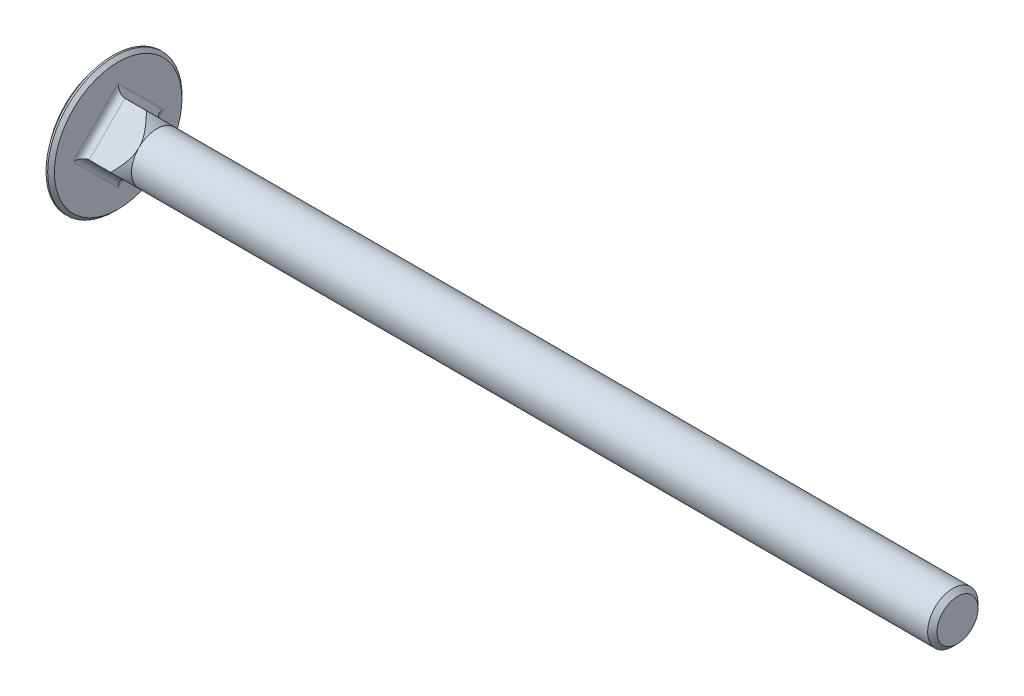
SolidWorks part; units mm, degrees
revolve "Base-Revolve" add sketch "BodySke" angle 360 about L6 other way angle 60
sketch "BodySke" plane through (0, 0, 0) normal (0, 0, 1) x (1, 0, 0)
  line L1 (3.0024, 8) -> (3.6, 8)
  line L2 (3.6, 8) -> (3.6, 3)
  line L3 (3.6, 3) -> (103.0455, 3)
  line L4 (103.6, 2.4455) -> (103.6, 0)
  line L5 (103.6, 0) -> (0, 0)
  line L6 (-31.75, 0) -> (127, 0) construction
  line L8 (103.6, 2.4455) -> (103.0455, 3)
  line L10 (103.6, -2.4455) -> (103.0455, -3) construction
  line L11 (4.6, 7.799) -> (4.6, 1.449) construction
  line L12 (85.6, 7.799) -> (85.6, 1.449) construction
  line L13 (3.6, 7.799) -> (3.6, 1.449) construction
  arc A0 (3.0024, 8) -> (0, 0) centre (12.1593, 0) ccw
  dimension "Diameter" = 6
  dimension "Head_dia" = 16
  dimension "Head_ht" = 3.6
  dimension "D1" = 0.5976
cosmetic thread "ThreadCosmetic" [suppressed] parameters "Thread_length"=18, "Thread_minor"=4.891
ref_plane "Plane1" through (0, 0, 0) normal (0, 0, 1) x (1, 0, 0)
ref_plane "Plane2" through (0, 0, 0) normal (0, 1, 0) x (1, 0, 0)
ref_plane "Plane3" through (0, 0, 0) normal (1, 0, 0) x (0, 0, -1)
sketch "Sketch1" plane through (3.6, 0, 0) normal (1, 0, 0) x (0, 0, -1)
  line L0 (0, 4.2426) -> (4.2426, 0)
  line L1 (4.2426, 0) -> (0, -4.2426)
  line L2 (0, -4.2426) -> (-4.2426, 0)
  line L3 (-4.2426, 0) -> (0, 4.2426)
  circle A0 centre (0, 0) radius 3 construction
  circle A1 centre (0, 0) radius 8 construction
  dimension "D1" = 6
extrude "Boss-Extrude1" add sketch "Sketch1" along normal blind 4.6
sketch "Sketch2" plane through (0, 0, 0) normal (0, 0, 1) x (1, 0, 0)
  line L0 (0, 0) -> (101.6, 0) construction
  line L1 (8.2, 3) -> (13.2, 3)
  line L2 (8.2, 3) -> (2.2, 9)
  line L3 (13.2, 3) -> (13.2, 9)
  line L4 (13.2, 9) -> (2.2, 9)
  dimension "D1" = 6
  dimension "D2" = 8.2
  dimension "D3" = 18
  dimension "D4" = 5
  dimension "D5" = 45
revolve "Cut-Revolve1" cut sketch "Sketch2" angle 360 about L0
fillet "Fillet1" radius 0.8 4 edges at (3.6, 2.1213, 2.1213) (3.6, -2.1213, 2.1213) (3.6, -2.1213, -2.1213) (3.6, 2.1213, -2.1213)
sketch "ThdSchSke" plane through (0, 0, 0) normal (0, 0, 1) x (1, 0, 0)
  line L0 (85.6, -2.4455) -> (85.2117, -3)
  line L1 (85.6, -2.4455) -> (85.9883, -3)
  line L2 (85.9883, -3) -> (85.9883, -3.75)
  line L3 (0, 0) -> (5.1513, 0) construction
  line L5 (85.9883, -3.75) -> (85.2117, -3.75)
  line L6 (85.2117, -3.75) -> (85.2117, -3)
  arc A0 (3.0024, 8) -> (3.0024, -8) centre (12.1593, 0) ccw construction
  dimension "Diameter" = 6
  dimension "Thread_minor" = 4.891
  dimension "Start" = 85.6
revolve "ThreadSchematic" [suppressed] cut sketch "ThdSchSke" angle 360 about L3
pattern_linear "ThdSchPat" [suppressed]
equation "\"Thread_minor@ThreadCosmetic\"  =  \"Minor_dia@BodySke\""
equation "\"Thread_length@ThreadCosmetic\" = ((sgn( (\"Length@BodySke\" - \"Advance@BodySke\" * 3.0) - \"Thread_nom@BodySke\" )-1)*( (\"Length@BodySke\" - \"Advance@BodySke\" * 3.0) - \"Thread_nom@BodySke\" ))/-2+ \"Thread_nom@BodySke\""
equation "\"Thread_minor@ThdSchSke\" = \"Minor_dia@BodySke\""
equation "\"Diameter@ThdSchSke\" = \"Diameter@BodySke\""
equation "\"Overcut@ThdSchSke\" = \"Diameter@BodySke\" * 1.25"
equation "\"Start@ThdSchSke\" = \"Head_ht@BodySke\" + \"Length@BodySke\" - \"Thread_length@ThreadCosmetic\"  '---Non-countersunk---"
equation "\"Num_threads@ThdSchPat\" = int( \"Thread_length@ThreadCosmetic\" / \"Advance@BodySke\" + 0.999 )  + 1"
equation "\"Advance@ThdSchPat\" = \"Thread_length@ThreadCosmetic\" /  (\"Num_threads@ThdSchPat\" - 1) 'relax it"
equation "\"Num_threads@ThdSchPat\" = \"Num_threads@ThdSchPat\" - sgn( \"Num_threads@ThdSchPat\" - 1) '---chamfered tips only---"
equation "\"D1@BodySke\" = \"Head_ht@BodySke\" * .166"
equation "\"D1@Sketch2\" = \"Diameter@BodySke\""
equation "\"D2@Sketch2\" = \"Head_ht@BodySke\" + \"NeckHt@Boss-Extrude1\""
equation "\"D3@Sketch2\" = \"Head_dia@BodySke\" + 2"
equation "\"D1@Sketch1\" = \"Diameter@BodySke\""
